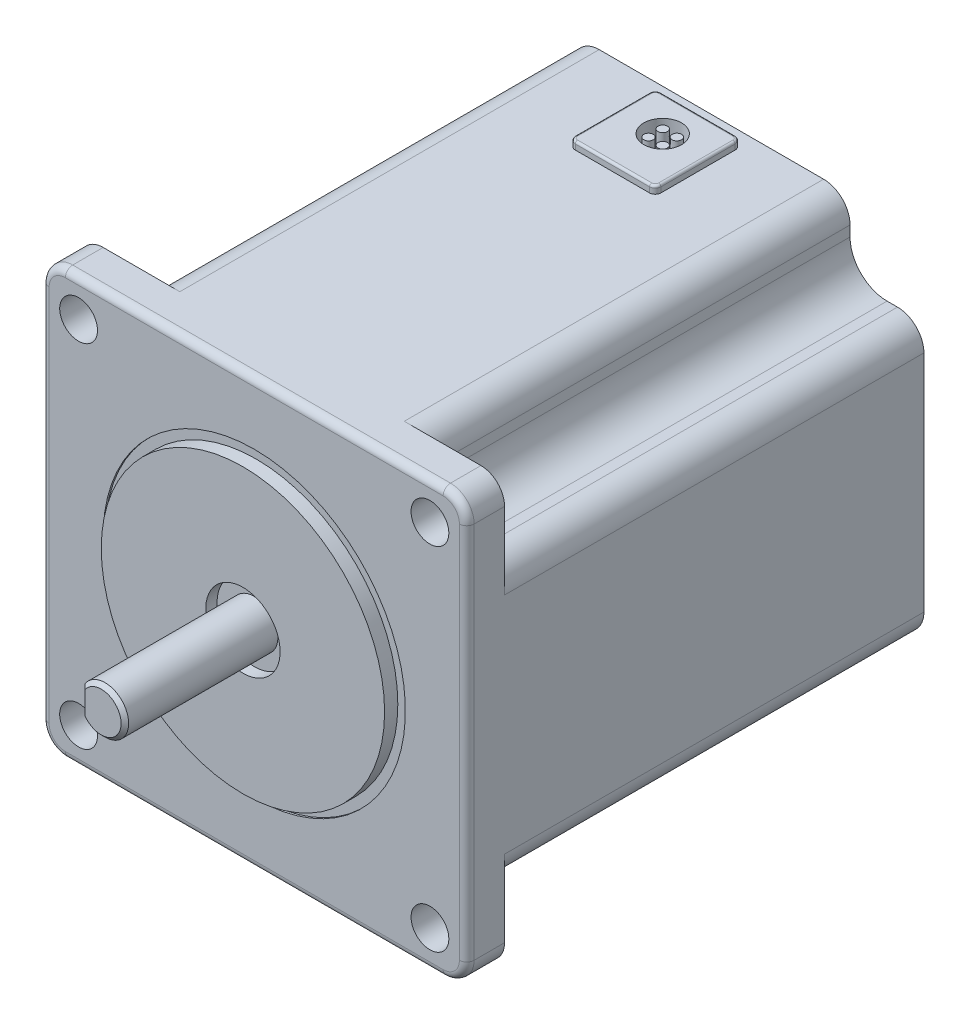
SolidWorks part; units mm, degrees
ref_plane "Front Plane" through (0, 0, 0) normal (0, 0, 1) x (1, 0, 0)
ref_plane "Top Plane" through (0, 0, 0) normal (0, 1, 0) x (1, 0, 0)
ref_plane "Right Plane" through (0, 0, 0) normal (1, 0, 0) x (0, 0, -1)
sketch "Sketch1" plane through (0, 0, 0) normal (0, 0, 1) x (1, 0, 0)
  line L0 (-2.667, -1.7227) -> (-2.667, 1.7227) construction
  line L1 (28.575, -28.575) -> (-28.575, -28.575) construction
  line L2 (28.575, -28.575) -> (28.575, 28.575) construction
  line L3 (28.575, 28.575) -> (-28.575, 28.575) construction
  line L4 (-28.575, -28.575) -> (-28.575, 28.575) construction
  line L5 (28.575, -28.575) -> (-28.575, 28.575) construction
  line L6 (28.575, 28.575) -> (-28.575, -28.575) construction
  line L7 (23.622, -23.622) -> (-23.622, -23.622) construction
  line L8 (23.622, -23.622) -> (23.622, 23.622) construction
  line L9 (23.622, 23.622) -> (-23.622, 23.622) construction
  line L10 (-23.622, -23.622) -> (-23.622, 23.622) construction
  line L11 (23.622, -23.622) -> (-23.622, 23.622) construction
  line L12 (23.622, 23.622) -> (-23.622, -23.622) construction
  circle A0 centre (-23.622, 23.622) radius 2.54 construction
  circle A1 centre (23.622, 23.622) radius 2.54 construction
  circle A2 centre (-23.622, -23.622) radius 2.54 construction
  circle A3 centre (23.622, -23.622) radius 2.54 construction
  circle A4 centre (0, 0) radius 3.175 construction
  circle A5 centre (0, 0) radius 19.05 construction
  point P0 (0, 0)
  point P6 (0, 0)
  point P18 (0, 3.175)
  point P19 (0, 28.575)
  point P20 (0, 19.05)
  point P21 (-23.622, -26.162)
  dimension "D3" = 5.08
  dimension "D4" = 6.35
  dimension "LargeDia" = 38.1
  dimension "Width" = 57.15
  dimension "CenterToCenter" = 47.244
  dimension "D6" = 5.842
sketch "Sketch2" plane through (0, 0, 0) normal (1, 0, 0) x (0, 0, -1)
  line L0 (0, 0) -> (56.388, 0) construction
  line L1 (0, 0) -> (-20.574, 0) construction
  line L2 (-20.574, -3.175) -> (-20.574, 3.175) construction
  line L3 (56.388, -28.575) -> (56.388, 28.575) construction
  line L4 (0, 28.575) -> (0, -28.575) construction
  line L5 (-1.524, 19.05) -> (-1.524, -19.05) construction
  line L6 (5.08, 28.575) -> (5.08, -28.575) construction
  point P3 (-1.524, 0)
  point P18 (5.08, 0)
  point P19 (-5.588, 0)
  dimension "Shaftlength" = 20.574
  dimension "D2" = 1.524
  dimension "D3" = 5.08
  dimension "D4" = 14.986
sketch "Sketch3" plane through (0, 0, 0) normal (0, 0, 1) x (1, 0, 0)
  line L1 (-28.575, -28.575) -> (-28.575, 28.575) construction
  line L2 (28.575, 28.575) -> (-28.575, 28.575) construction
  line L3 (28.575, -28.575) -> (28.575, 28.575) construction
  line L4 (28.575, -28.575) -> (-28.575, -28.575) construction
  line L5 (-28.575, -25.4) -> (-28.575, 25.4)
  line L6 (25.4, 28.575) -> (-25.4, 28.575)
  line L7 (28.575, -25.4) -> (28.575, 25.4)
  line L8 (25.4, -28.575) -> (-25.4, -28.575)
  arc A4 (-28.575, 25.4) -> (-25.4, 28.575) centre (-25.4, 25.4) cw
  arc A5 (25.4, 28.575) -> (28.575, 25.4) centre (25.4, 25.4) cw
  arc A6 (28.575, -25.4) -> (25.4, -28.575) centre (25.4, -25.4) cw
  arc A7 (-25.4, -28.575) -> (-28.575, -25.4) centre (-25.4, -25.4) cw
  dimension "D1" = 3.175
extrude "Boss-Extrude1" add sketch "Sketch3" against normal up to vertex (5.08 mm away) up to point (0, 0, -5.08)
fillet "Fillet1" radius 0.9906 8 edges at (0, 28.575, 0) (28.575, 0, 0) (0, -28.575, 0) (-28.575, 0, 0) (27.6451, 27.6451, 0) (27.6451, -27.6451, 0) (-27.6451, -27.6451, 0) (-27.6451, 27.6451, 0)
sketch "Sketch4" plane through (0, 0, -5.08) normal (0, 0, 1) x (1, 0, 0)
  line L0 (0, 28.575) -> (0, 0) construction
  line L1 (0, 0) -> (-28.575, 0) construction
  line L2 (-25.019, 18.6436) -> (-23.622, 18.6436)
  line L3 (-18.6436, 23.622) -> (-18.6436, 25.019)
  line L4 (-28.575, 25.4) -> (-28.575, -25.4)
  line L5 (25.4, 28.575) -> (-25.4, 28.575)
  line L6 (28.575, -25.4) -> (28.575, 25.4)
  line L7 (-25.4, -28.575) -> (25.4, -28.575)
  line L8 (-28.575, 15.0876) -> (-28.575, -15.0876)
  line L9 (15.0876, 28.575) -> (-15.0876, 28.575)
  line L10 (28.575, -15.0876) -> (28.575, 15.0876)
  line L14 (28.575, 28.575) -> (-28.575, 28.575) construction
  line L15 (18.6436, 23.622) -> (18.6436, 25.019)
  line L16 (25.019, 18.6436) -> (23.622, 18.6436)
  line L17 (25.019, -18.6436) -> (23.622, -18.6436)
  line L18 (18.6436, -23.622) -> (18.6436, -25.019)
  line L19 (15.0876, -28.575) -> (-15.0876, -28.575)
  line L20 (-18.6436, -23.622) -> (-18.6436, -25.019)
  line L21 (-25.019, -18.6436) -> (-23.622, -18.6436)
  arc A0 (-25.019, 18.6436) -> (-28.575, 15.0876) centre (-25.019, 15.0876) ccw
  arc A1 (-15.0876, 28.575) -> (-18.6436, 25.019) centre (-15.0876, 25.019) ccw
  arc A2 (-23.622, 18.6436) -> (-18.6436, 23.622) centre (-23.622, 23.622) ccw
  arc A3 (23.622, 18.6436) -> (18.6436, 23.622) centre (23.622, 23.622) cw
  arc A4 (-25.4, 28.575) -> (-28.575, 25.4) centre (-25.4, 25.4) ccw
  arc A5 (15.0876, 28.575) -> (18.6436, 25.019) centre (15.0876, 25.019) cw
  arc A6 (28.575, 25.4) -> (25.4, 28.575) centre (25.4, 25.4) ccw
  arc A7 (25.019, 18.6436) -> (28.575, 15.0876) centre (25.019, 15.0876) cw
  arc A8 (25.4, -28.575) -> (28.575, -25.4) centre (25.4, -25.4) ccw
  arc A10 (-28.575, -25.4) -> (-25.4, -28.575) centre (-25.4, -25.4) ccw
  arc A11 (25.019, -18.6436) -> (28.575, -15.0876) centre (25.019, -15.0876) ccw
  arc A12 (15.0876, -28.575) -> (18.6436, -25.019) centre (15.0876, -25.019) ccw
  arc A13 (23.622, -18.6436) -> (18.6436, -23.622) centre (23.622, -23.622) ccw
  arc A14 (-23.622, -18.6436) -> (-18.6436, -23.622) centre (-23.622, -23.622) cw
  arc A15 (-15.0876, -28.575) -> (-18.6436, -25.019) centre (-15.0876, -25.019) cw
  arc A16 (-25.019, -18.6436) -> (-28.575, -15.0876) centre (-25.019, -15.0876) cw
  dimension "D2" = 4.9784
  dimension "D3" = 3.556
  dimension "D1" = 0
extrude "Boss-Extrude2" add sketch "Sketch4" against normal blind 56.388
sketch "Sketch5" plane through (0, 0, 0) normal (1, 0, 0) x (0, 0, -1)
  line L1 (0, 0) -> (-1.524, 0)
  line L2 (0, 0) -> (0, 19.05)
  line L3 (0, 19.05) -> (-1.524, 19.05)
  line L4 (-1.524, 0) -> (-1.524, 19.05)
revolve "Revolve1" add sketch "Sketch5" angle 360 about L1
sketch "Sketch6" plane through (0, 0, 0) normal (1, 0, 0) x (0, 0, -1)
  line L0 (-20.574, 0) -> (-1.524, 0) construction
  line L1 (56.388, 0) -> (-1.524, 0)
  line L2 (56.388, 0) -> (56.388, 3.175)
  line L3 (0, 5) -> (-1.524, 5)
  line L4 (-1.524, 0) -> (-1.524, 5)
  line L5 (56.388, 3.175) -> (0, 3.175)
  line L6 (0, 3.175) -> (0, 5)
  line L10 (0, 20.32) -> (0.254, 20.32)
  line L11 (0, 20.32) -> (0, 19.05)
  line L12 (0, 19.05) -> (0.254, 19.05)
  line L13 (0.254, 20.32) -> (0.254, 19.05)
  dimension "D1" = 10
  dimension "D2" = 40.64
  dimension "D3" = 0.254
revolve "Cut-Revolve1" cut sketch "Sketch6" angle 360 about L0
sketch "Sketch7" plane through (0, 0, 0) normal (1, 0, 0) x (0, 0, -1)
  line L1 (-20.574, 3.175) -> (56.388, 3.175)
  line L2 (-20.574, 3.175) -> (-20.574, 0)
  line L3 (-20.574, 0) -> (56.388, 0)
  line L4 (56.388, 3.175) -> (56.388, 0)
revolve "Revolve2" add sketch "Sketch7" angle 360 about L3
sketch "Sketch8" plane through (0, 0, 20.574) normal (0, 0, 1) x (1, 0, 0)
  line L0 (-2.667, -1.7227) -> (-2.667, 1.7227) construction
  line L1 (-2.667, -1.7227) -> (-2.667, 1.7227)
  circle A0 centre (0, 0) radius 3.175 construction
  arc A1 (-2.667, 1.7227) -> (-2.667, -1.7227) centre (0, 0) ccw
extrude "Cut-Extrude1" cut sketch "Sketch8" against normal up to vertex (14.986 mm away) up to point (0, 0, 5.588)
chamfer "Chamfer1" distance 0.508 angle 45 3 edges at (0, -3.175, -56.388) (3.175, 0, 20.574) (-2.667, 0, 20.574)
sketch "Sketch9" plane through (0, 0, 0) normal (0, 0, 1) x (1, 0, 0)
  circle A0 centre (23.622, -23.622) radius 2.54 construction
  circle A1 centre (23.622, -23.622) radius 2.54
  circle A2 centre (-23.622, -23.622) radius 2.54 construction
  circle A3 centre (-23.622, 23.622) radius 2.54 construction
  circle A4 centre (23.622, 23.622) radius 2.54 construction
  circle A5 centre (-23.622, -23.622) radius 2.54
  circle A6 centre (-23.622, 23.622) radius 2.54
  circle A7 centre (23.622, 23.622) radius 2.54
extrude "Cut-Extrude2" cut sketch "Sketch9" against normal up to next (5.08 mm away)
sketch "Sketch10" plane through (0, 28.575, -0.7512) normal (0, 1, 0) x (1, 0, 0)
  line L0 (0, -0.7512) -> (0, 54.1687) construction
  line L2 (-3.8354, 54.1687) -> (-3.8354, 49.2157)
  line L3 (-3.8354, 49.2157) -> (3.8354, 49.2157)
  line L4 (3.8354, 54.1687) -> (3.8354, 49.2157)
  line L5 (25.4, -0.7512) -> (-25.4, -0.7512) construction
  line L7 (15.0876, 60.7168) -> (-15.0876, 60.7168) construction
  arc A0 (3.8354, 54.1687) -> (-3.8354, 54.1687) centre (0, 54.1687) ccw
  dimension "D1" = 7.6708
  dimension "D2" = 4.953
  dimension "D3" = 6.5481
extrude "Cut-Extrude3" cut sketch "Sketch10" against normal blind 1.2954
sketch "Sketch11" plane through (0, 27.2796, 0) normal (0, 1, 0) x (1, 0, 0)
  circle A0 centre (0, 54.9199) radius 2.54
  circle A1 centre (0, 54.9199) radius 3.7465
  dimension "D1" = 5.08
  dimension "D2" = 7.493
extrude "Boss-Extrude3" add sketch "Sketch11" along normal up to surface (1.2954 mm away) up to face at (0, 28.575, -53.4022)
sketch "Sketch12" plane through (0, 28.575, 0) normal (0, 1, 0) x (1, 0, 0)
  line L0 (0, 53.9166) -> (0, 0) construction
  line L1 (-5.7531, 48.1635) -> (5.7531, 48.1635)
  line L2 (-5.7531, 48.1635) -> (-5.7531, 59.6697)
  line L3 (-5.7531, 59.6697) -> (5.7531, 59.6697)
  line L4 (5.7531, 48.1635) -> (5.7531, 59.6697)
  line L5 (-5.7531, 48.1635) -> (5.7531, 59.6697) construction
  line L6 (-5.7531, 59.6697) -> (5.7531, 48.1635) construction
  circle A2 centre (0, 54.9199) radius 2.54 construction
  circle A3 centre (0, 54.9199) radius 2.54
  point P0 (0, 53.9166)
  dimension "D2" = 4.7498
  dimension "D1" = 11.5062
extrude "Boss-Extrude4" add sketch "Sketch12" along normal blind 1.016
fillet "Fillet2" radius 0.762 4 edges at (5.7531, 29.083, -59.6697) (-5.7531, 29.083, -59.6697) (5.7531, 29.083, -48.1635) (-5.7531, 29.083, -48.1635)
fillet "Fillet3" radius 0.3048 8 edges at (-5.5299, 29.591, -48.3867) (-5.7531, 29.591, -53.9166) (-5.5299, 29.591, -59.4465) (0, 29.591, -59.6697) (5.5299, 29.591, -59.4465) (5.7531, 29.591, -53.9166) (5.5299, 29.591, -48.3867) (0, 29.591, -48.1635)
sketch "Sketch13" plane through (0, 27.2796, 0) normal (0, 1, 0) x (1, 0, 0)
  line L4 (-0.9525, 53.9674) -> (0.9525, 53.9674) construction
  line L5 (-0.9525, 53.9674) -> (-0.9525, 55.8724) construction
  line L6 (-0.9525, 55.8724) -> (0.9525, 55.8724) construction
  line L7 (0.9525, 53.9674) -> (0.9525, 55.8724) construction
  line L8 (-0.9525, 53.9674) -> (0.9525, 55.8724) construction
  line L9 (-0.9525, 55.8724) -> (0.9525, 53.9674) construction
  circle A0 centre (-0.9525, 55.8724) radius 0.635
  circle A1 centre (0.9525, 55.8724) radius 0.635
  circle A2 centre (0.9525, 53.9674) radius 0.635
  circle A3 centre (-0.9525, 53.9674) radius 0.635
  circle A4 centre (0, 54.9199) radius 2.54 construction
  point P8 (0, 54.9199)
  dimension "D1" = 1.27
  dimension "D2" = 1.905
extrude "Boss-Extrude5" add sketch "Sketch13" along normal blind 1.9304
equation "\"D1@Boss-Extrude2\"=\"A@Sketch2\""
